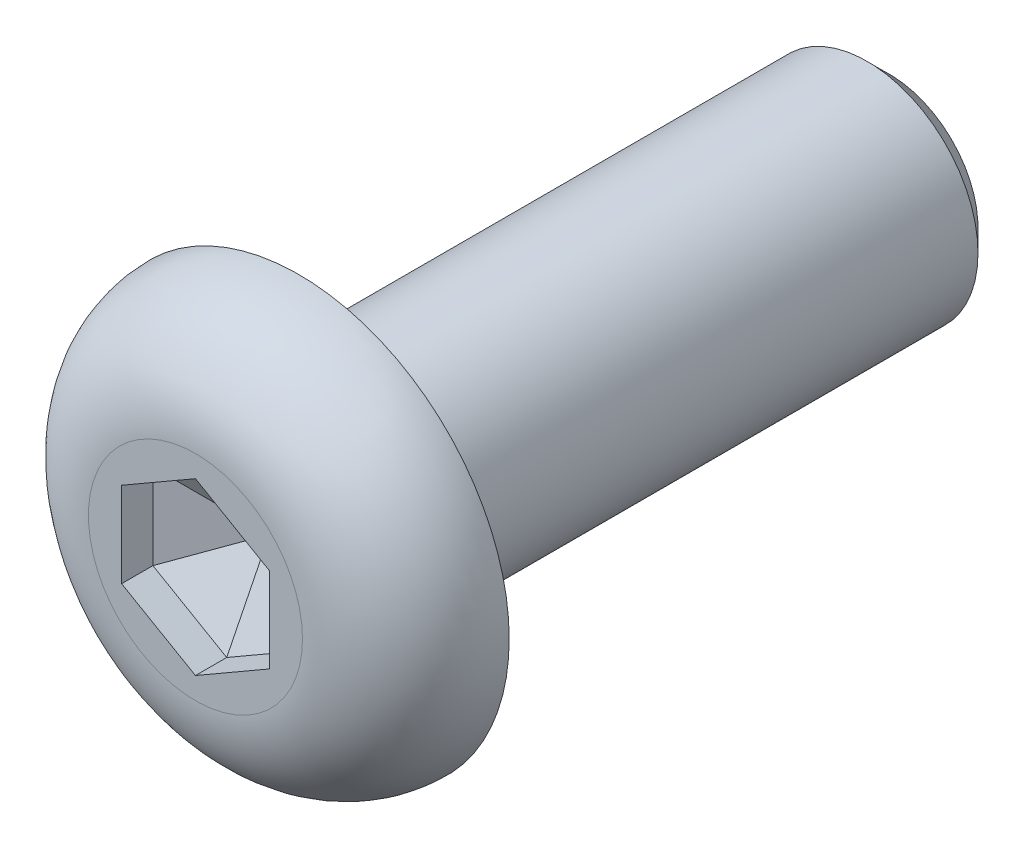
SolidWorks part; units mm, degrees
ref_plane "前视基准面" through (0, 0, 0) normal (0, 0, 1) x (1, 0, 0)
ref_plane "上视基准面" through (0, 0, 0) normal (0, 1, 0) x (1, 0, 0)
ref_plane "右视基准面" through (0, 0, 0) normal (1, 0, 0) x (0, 0, -1)
sketch "草图1" plane through (0, 0, 0) normal (0, 0, 1) x (1, 0, 0)
  circle A0 centre (0, 0) radius 2.85
  dimension "dk" = 5.7
extrude "凸台-拉伸1" add sketch "草图1" along normal blind 1.4
ref_axis "基准轴1" through (0, 0, 1.4) along (0, 0, -1)
fillet "圆角1" radius 1.4 1 edges at (2.85, 0, 1.4)
sketch "草图3" plane through (0, 0, 0) normal (0, 0, -1) x (-1, 0, 0)
  circle A0 centre (0, 0) radius 1.5
  dimension "d" = 3
extrude "凸台-拉伸3" add sketch "草图3" along normal blind 8
cosmetic thread "装饰螺纹线1" parameters "b"=11.9, "D2"=2.459
sketch "草图4" plane through (0, 0, 1.4) normal (0, 0, 1) x (1, 0, 0)
  line L1 (1, 0.5774) -> (0, 1.1547)
  line L2 (0, 1.1547) -> (-1, 0.5774)
  line L3 (-1, 0.5774) -> (-1, -0.5774)
  line L4 (-1, -0.5774) -> (0, -1.1547)
  line L5 (0, -1.1547) -> (1, -0.5774)
  line L6 (1, -0.5774) -> (1, 0.5774)
  circle A0 centre (0, 0) radius 1 construction
  dimension "s" = 2
extrude "切除-拉伸1" cut sketch "草图4" against normal blind 1
chamfer "倒角2" distance 0.3 angle 45 1 edges at (-1.5, 0, -8)
chamfer "倒角3" distance 0.5764 angle 60 6 edges at (-0.5, -0.866, 0.4) (-1, 0, 0.4) (-0.5, 0.866, 0.4) (0.5, 0.866, 0.4) (0.5, -0.866, 0.4) (1, 0, 0.4) first distance on face at (-0.5, -0.866, 0.9) first distance on face at (-1, 0, 0.9) first distance on face at (-0.5, 0.866, 0.9) first distance on face at (0.5, 0.866, 0.9) first distance on face at (0.5, -0.866, 0.9) first distance on face at (1, 0, 0.9)
fillet "圆角2" radius 0.1 1 edges at (1.5, 0, 0)
ref_plane "基准面1" through (0, 0, 0) normal (0, 0, -1) x (-1, 0, 0)
equation "\"D1@倒角3\"=\"s@草图4\" /3.47"
equation "\"D1@倒角2\"= \"d@草图3\" / 10"
equation "\"D1@圆角1\"=\"k@凸台-拉伸1\""
